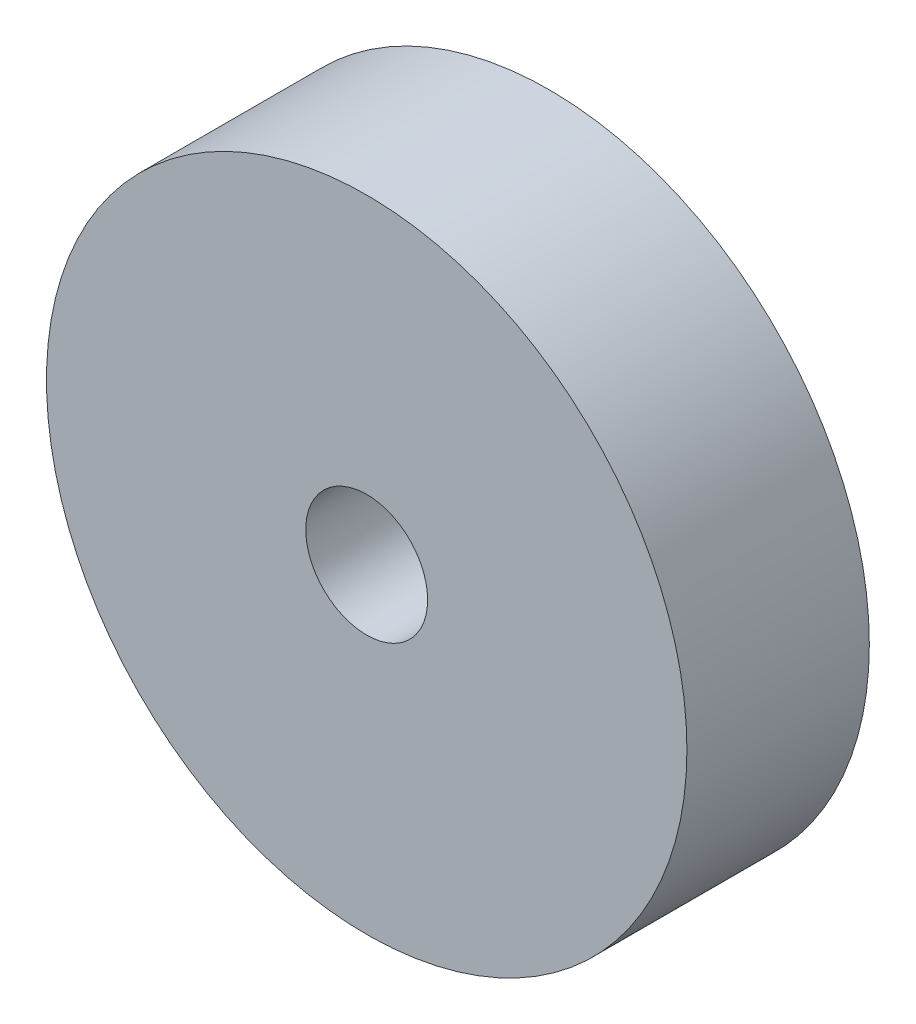
SolidWorks part; units mm, degrees
ref_plane "Front Plane" through (0, 0, 0) normal (0, 0, 1) x (1, 0, 0)
ref_plane "Top Plane" through (0, 0, 0) normal (0, 1, 0) x (1, 0, 0)
ref_plane "Right Plane" through (0, 0, 0) normal (1, 0, 0) x (0, 0, -1)
sketch "Sketch1" plane through (0, 0, 0) normal (0, 0, 1) x (1, 0, 0)
  circle A0 centre (0, 0) radius 9.8091
  circle A1 centre (0, 0) radius 1.8669
  dimension "D1" = 19.6182
  dimension "D2" = 3.7338
extrude "Boss-Extrude1" add sketch "Sketch1" along normal blind 5.588
